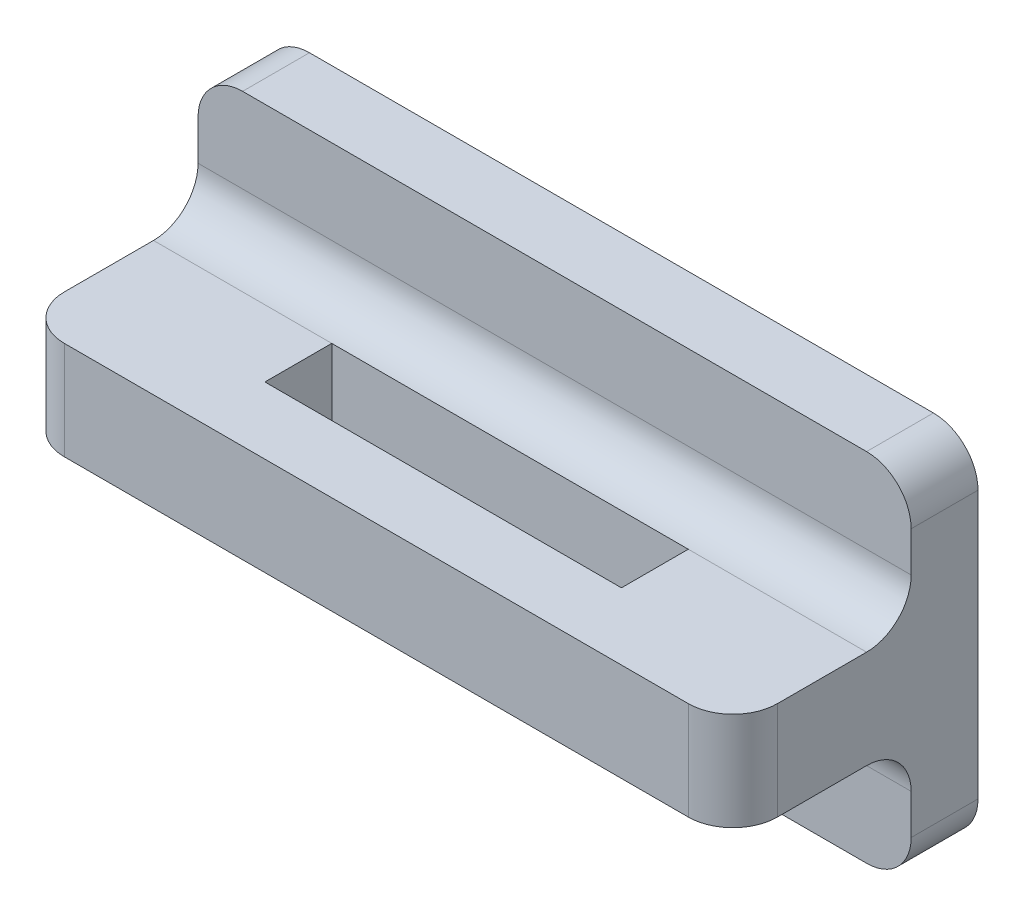
SolidWorks part; units mm, degrees
material "ABS"
ref_plane "X-Y Datum" through (0, 0, 0) normal (0, 0, 1) x (1, 0, 0)
ref_plane "X-Z Datum" through (0, 0, 0) normal (0, 1, 0) x (1, 0, 0)
ref_plane "Y-Z Datum" through (0, 0, 0) normal (1, 0, 0) x (0, 0, -1)
sketch "Sketch1" plane through (0, 0, 0) normal (0, 0, 1) x (1, 0, 0)
  line L1 (-25.4, 12.7) -> (25.4, 12.7)
  line L2 (-25.4, 12.7) -> (-25.4, -12.7)
  line L3 (-25.4, -12.7) -> (25.4, -12.7)
  line L4 (25.4, 12.7) -> (25.4, -12.7)
  line L5 (-25.4, 12.7) -> (25.4, -12.7) construction
  line L6 (-25.4, -12.7) -> (25.4, 12.7) construction
  point P0 (0, 0)
  dimension "D1" = 50.8
  dimension "D2" = 25.4
extrude "Boss-Extrude1" add sketch "Sketch1" along normal blind 4.7625
sketch "Sketch2" plane through (0, 0, 4.7625) normal (0, 0, 1) x (1, 0, 0)
  line L0 (25.4, -12.7) -> (25.4, 12.7) construction
  line L1 (-25.4, 3.5) -> (25.4, 3.5)
  line L2 (-25.4, 3.5) -> (-25.4, -3.5)
  line L3 (-25.4, -3.5) -> (25.4, -3.5)
  line L4 (25.4, 3.5) -> (25.4, -3.5)
  line L5 (-25.4, 3.5) -> (25.4, -3.5) construction
  line L6 (-25.4, -3.5) -> (25.4, 3.5) construction
  point P0 (0, 0)
  dimension "D1" = 7
extrude "Boss-Extrude2" add sketch "Sketch2" along normal blind 12.7
fillet "Fillet1" radius 3.175 8 edges at (0, 3.5, 4.7625) (0, -3.5, 4.7625) (-25.4, 0, 17.4625) (25.4, 0, 17.4625) (25.4, 12.7, 2.3813) (25.4, -12.7, 2.3813) (-25.4, 12.7, 2.3813) (-25.4, -12.7, 2.3813)
sketch "Sketch3" plane through (0, -3.5, 0) normal (0, -1, 0) x (1, 0, 0)
  line L0 (0, 0) -> (0, 17.4625) construction
  line L1 (-22.225, 17.4625) -> (22.225, 17.4625) construction
  line L3 (-12.7, 12.7) -> (12.7, 12.7)
  line L4 (-12.7, 12.7) -> (-12.7, 7.9375)
  line L5 (-12.7, 7.9375) -> (12.7, 7.9375)
  line L6 (12.7, 12.7) -> (12.7, 7.9375)
  line L7 (-12.7, 12.7) -> (12.7, 7.9375) construction
  line L8 (-12.7, 7.9375) -> (12.7, 12.7) construction
  point P5 (0, 10.3187)
  dimension "D1" = 25.4
  dimension "D2" = 4.7625
  dimension "D3" = 4.7625
extrude "Cut-Extrude1" cut sketch "Sketch3" against normal through all
